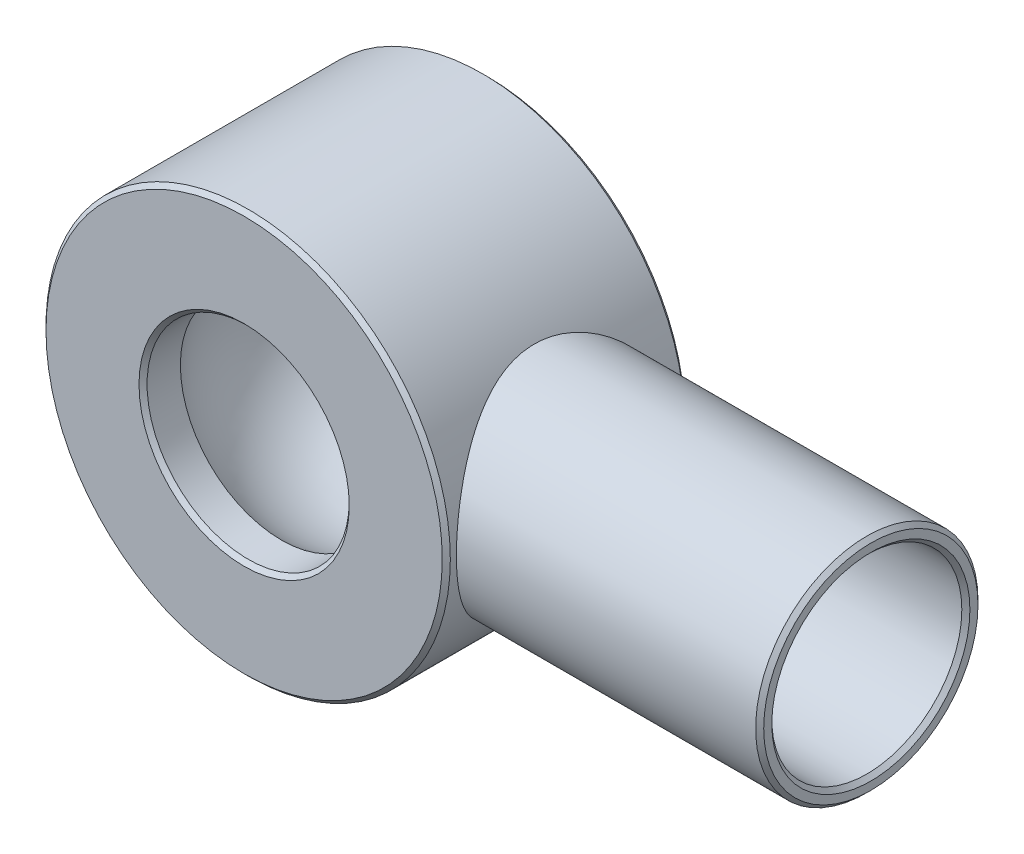
SolidWorks part; units mm, degrees
ref_plane "Front Plane" through (0, 0, 0) normal (0, 0, 1) x (1, 0, 0)
ref_plane "Top Plane" through (0, 0, 0) normal (0, 1, 0) x (1, 0, 0)
ref_plane "Right Plane" through (0, 0, 0) normal (1, 0, 0) x (0, 0, -1)
sketch "Sketch3" plane through (0, 0, 0) normal (0, 0, 1) x (1, 0, 0)
  circle A0 centre (0, 0) radius 25
  circle A1 centre (0, 0) radius 50
  dimension "D1" = 50
  dimension "D2" = 100
extrude "Boss-Extrude1" add sketch "Sketch3" along normal blind 30 and the other way blind 30
sketch "Sketch4" plane through (0, 0, 0) normal (1, 0, 0) x (0, 0, -1)
  line L0 (0, 32.5) -> (0, -32.5)
  arc A7 (0, -32.5) -> (0, 32.5) centre (0, 0) ccw
  dimension "D2" = 65
  dimension "D1" = 65
revolve "Cut-Revolve5" cut sketch "Sketch4" angle 360 about L0
ref_plane "Plane1" through (125, 0, 0) normal (1, 0, 0) x (0, 0, -1)
sketch "Sketch5" plane through (125, 0, 0) normal (1, 0, 0) x (0, 0, -1)
  circle A0 centre (0, 0) radius 27.5
  dimension "D1" = 55
extrude "Boss-Extrude2" add sketch "Sketch5" against normal blind 90
sketch "Sketch6" plane through (125, 0, 0) normal (1, 0, 0) x (0, 0, -1)
  circle A0 centre (0, 0) radius 23.5
  dimension "D1" = 47
extrude "Cut-Extrude1" cut sketch "Sketch6" against normal blind 35
chamfer "Chamfer1" distance 1 angle 45 1 edges at (50, 0, -30)
chamfer "Chamfer3" distance 1 angle 45 1 edges at (25, 0, -30)
chamfer "Chamfer5" distance 1 angle 45 1 edges at (50, 0, 30)
chamfer "Chamfer6" distance 1 angle 45 1 edges at (25, 0, 30)
chamfer "Chamfer7" distance 1 angle 45 2 edges at (125, 0, -23.5) (125, 0, -27.5)
